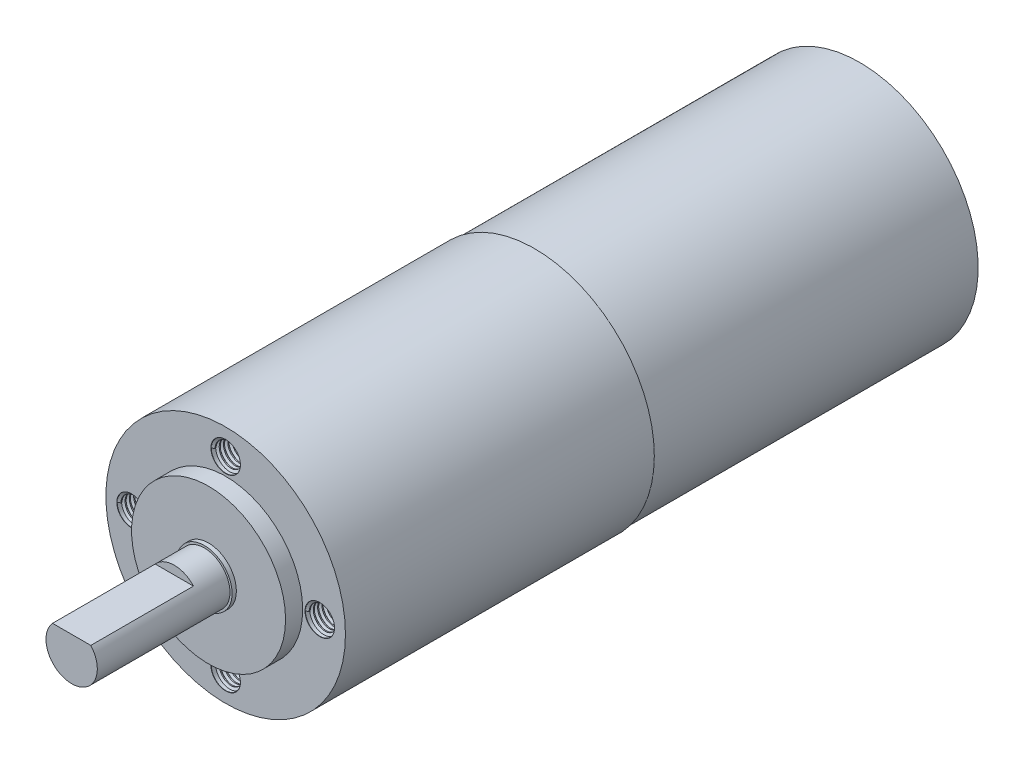
SolidWorks part; units mm, degrees
ref_plane "Front Plane" through (0, 0, 0) normal (0, 0, 1) x (1, 0, 0)
ref_plane "Top Plane" through (0, 0, 0) normal (0, 1, 0) x (1, 0, 0)
ref_plane "Right Plane" through (0, 0, 0) normal (1, 0, 0) x (0, 0, -1)
sketch "Sketch1" plane through (0, 0, 0) normal (0, 0, 1) x (1, 0, 0)
  circle A0 centre (0, 0) radius 14
  dimension "D1" = 28
extrude "Boss-Extrude1" add sketch "Sketch1" against normal blind 36.1
sketch "Sketch2" plane through (0, 0, -36.1) normal (0, 0, -1) x (-1, 0, 0)
  circle A0 centre (0, 0) radius 13.85
  dimension "D1" = 27.7
extrude "Boss-Extrude2" add sketch "Sketch2" along normal blind 38
sketch "Sketch3" plane through (0, 0, 0) normal (0, 0, 1) x (1, 0, 0)
  circle A0 centre (0, 0) radius 9
  dimension "D1" = 18
extrude "Boss-Extrude3" add sketch "Sketch3" along normal blind 2
sketch "Sketch4" plane through (0, 0, 0) normal (0, 0, 1) x (1, 0, 0)
  circle A0 centre (0, 0) radius 11
  point P4 (0, 11)
  point P6 (-11, 0)
  point P8 (0, -11)
  point P10 (11, 0)
  dimension "D1" = 22
hole_wizard "M3 Clearance Hole1" positions "Sketch4" profile "Sketch6" hole size "M3" standard "ANSI Metric"
sketch "Sketch6" plane through (11, 0, 0) normal (1, 0, 0) x (0, -1, 0)
  line L0 (0, 0) -> (0, 13.0215)
  line L1 (0, 13.0215) -> (1.7, 12)
  line L2 (1.7, 12) -> (1.7, 0.021)
  line L3 (1.7, 0.021) -> (1.725, 0)
  line L5 (1.725, 0) -> (0, 0)
  line L6 (-1.7, 0.021) -> (-1.725, 0) construction
  line L10 (0, 13.0215) -> (-1.7, 12) construction
  line L11 (0, -6.35) -> (0, 107.95) construction
  dimension "Hole Dia." = 3.4
  dimension "Hole Depth" = 12
  dimension "Near C'Sink Dia." = 3.45
  dimension "Near C'Sink Angle" = 100
  dimension "Drill Angle" = 118
thread "Thread1" pitch 0.5 method extrude profile "Thread Profile2" start angle 0, offset 0, length 10, pitch 0.5, diameter 3.4
ref_plane "Plane2" through (-12.7, 0, -0.021) normal (0, -1, 0) x (-1, 0, 0)
sketch "Thread Profile2" plane through (-12.7, 0, -0.021) normal (0, -1, 0) x (-1, 0, 0)
  line L0 (0, 0) -> (0, 0.5) construction
  line L11 (0, 0) -> (0, 0.4375)
  line L12 (0, 0.4375) -> (-0.2706, 0.2812)
  line L13 (-0.2706, 0.2812) -> (-0.2706, 0.1562)
  line L15 (-0.2706, 0.1562) -> (0, 0)
  line L17 (-0.2706, 0.2187) -> (0, 0.2187) construction
  point P2 (0, 0)
  dimension "Pitch" = 0.5
  dimension "Profile_Angle" = 60
  dimension "Profile_Land" = 0.125
  dimension "Profile_Height" = 0.2706
thread "Thread2" pitch 0.5 method extrude profile "Thread Profile3" start angle 0, offset 0, length 10, pitch 0.5, diameter 3.4
ref_plane "Plane3" through (-1.7, 11, -0.021) normal (0, -1, 0) x (-1, 0, 0)
sketch "Thread Profile3" plane through (-1.7, 11, -0.021) normal (0, -1, 0) x (-1, 0, 0)
  line L0 (0, 0) -> (0, 0.5) construction
  line L11 (0, 0) -> (0, 0.4375)
  line L12 (0, 0.4375) -> (-0.2706, 0.2812)
  line L13 (-0.2706, 0.2812) -> (-0.2706, 0.1562)
  line L15 (-0.2706, 0.1562) -> (0, 0)
  line L17 (-0.2706, 0.2187) -> (0, 0.2187) construction
  point P2 (0, 0)
  dimension "Pitch" = 0.5
  dimension "Profile_Angle" = 60
  dimension "Profile_Land" = 0.125
  dimension "Profile_Height" = 0.2706
thread "Thread3" pitch 0.5 method extrude profile "Thread Profile4" start angle 0, offset 0, length 10, pitch 0.5, diameter 3.4
ref_plane "Plane4" through (9.3, 0, -0.021) normal (0, -1, 0) x (-1, 0, 0)
sketch "Thread Profile4" plane through (9.3, 0, -0.021) normal (0, -1, 0) x (-1, 0, 0)
  line L0 (0, 0) -> (0, 0.5) construction
  line L11 (0, 0) -> (0, 0.4375)
  line L12 (0, 0.4375) -> (-0.2706, 0.2812)
  line L13 (-0.2706, 0.2812) -> (-0.2706, 0.1562)
  line L15 (-0.2706, 0.1562) -> (0, 0)
  line L17 (-0.2706, 0.2187) -> (0, 0.2187) construction
  point P2 (0, 0)
  dimension "Pitch" = 0.5
  dimension "Profile_Angle" = 60
  dimension "Profile_Land" = 0.125
  dimension "Profile_Height" = 0.2706
thread "Thread4" pitch 0.5 method extrude profile "Thread Profile5" start angle 0, offset 0, length 10, pitch 0.5, diameter 3.4
ref_plane "Plane5" through (-1.7, -11, -0.021) normal (0, -1, 0) x (-1, 0, 0)
sketch "Thread Profile5" plane through (-1.7, -11, -0.021) normal (0, -1, 0) x (-1, 0, 0)
  line L0 (0, 0) -> (0, 0.5) construction
  line L11 (0, 0) -> (0, 0.4375)
  line L12 (0, 0.4375) -> (-0.2706, 0.2812)
  line L13 (-0.2706, 0.2812) -> (-0.2706, 0.1562)
  line L15 (-0.2706, 0.1562) -> (0, 0)
  line L17 (-0.2706, 0.2187) -> (0, 0.2187) construction
  point P2 (0, 0)
  dimension "Pitch" = 0.5
  dimension "Profile_Angle" = 60
  dimension "Profile_Land" = 0.125
  dimension "Profile_Height" = 0.2706
sketch "Sketch22" plane through (0, 0, 2) normal (0, 0, 1) x (1, 0, 0)
  circle A0 centre (0, 0) radius 3.25
  dimension "D1" = 6.5
extrude "Boss-Extrude4" add sketch "Sketch22" along normal blind 0.5 contours A0
sketch "Sketch23" plane through (0, 0, 2.5) normal (0, 0, 1) x (1, 0, 0)
  circle A0 centre (0, 0) radius 3
  dimension "D1" = 6
extrude "Boss-Extrude5" add sketch "Sketch23" along normal blind 15.5
sketch "Sketch24" plane through (0, 0, 18) normal (0, 0, 1) x (1, 0, 0)
  line L0 (-3, 2) -> (3, 2)
  line L1 (-3, 3) -> (3, 3)
  line L2 (-3, 3) -> (-3, 2)
  line L4 (3, 3) -> (3, 2)
  circle A0 centre (0, 0) radius 3 construction
  point P0 (0, 0)
  point P10 (0, 0)
  point P11 (0, 0)
  point P12 (0, 0)
  point P13 (0, 0)
  point P14 (0, 0)
  point P15 (0, 0)
  point P16 (3, 3)
  point P17 (3, 3)
extrude "Cut-Extrude1" cut sketch "Sketch24" against normal blind 12 contours L1 L4 L0 L2
